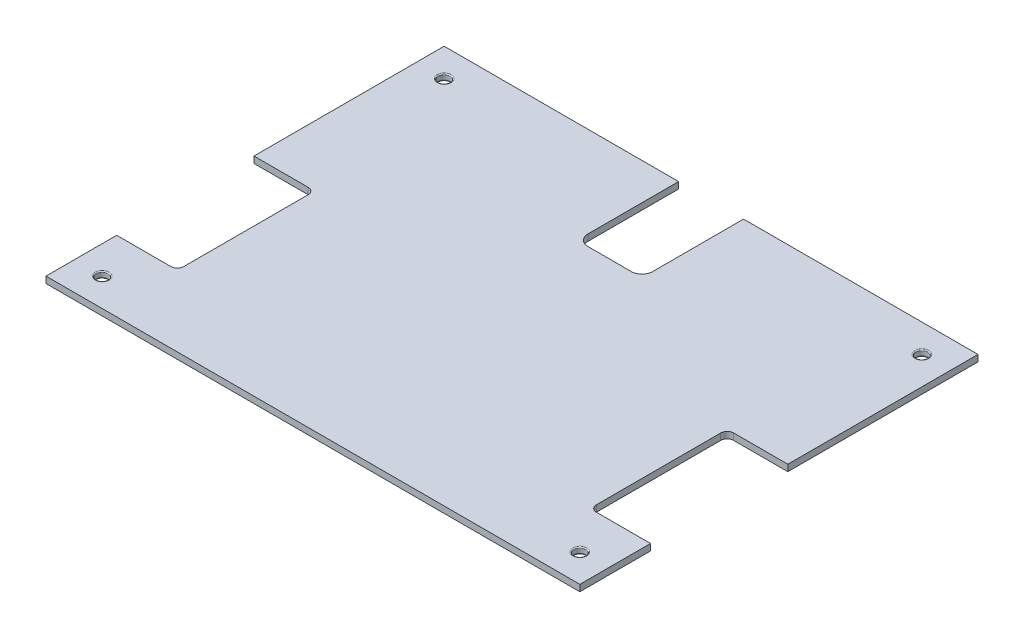
SolidWorks part; units mm, degrees
ref_plane "Front Plane" through (0, 0, 0) normal (0, 0, 1) x (1, 0, 0)
ref_plane "Top Plane" through (0, 0, 0) normal (0, 1, 0) x (1, 0, 0)
ref_plane "Right Plane" through (0, 0, 0) normal (1, 0, 0) x (0, 0, -1)
sketch "Sketch1" plane through (0, 0, 0) normal (0, 1, 0) x (1, 0, 0)
  line L1 (-123.65, -92.225) -> (123.65, -92.225)
  line L2 (-123.65, -92.225) -> (-123.65, 92.225)
  line L3 (-123.65, 92.225) -> (123.65, 92.225)
  line L4 (123.65, -92.225) -> (123.65, 92.225)
  line L5 (-123.65, -92.225) -> (123.65, 92.225) construction
  line L6 (-123.65, 92.225) -> (123.65, -92.225) construction
  point P0 (0, 0)
  dimension "D1" = 247.3
  dimension "D2" = 184.45
extrude "Boss-Extrude1" add sketch "Sketch1" along normal blind 3
sketch "Sketch4" [suppressed] plane through (0, 3, 0) normal (0, 1, 0) x (1, 0, 0)
  line L0 (0, 0) -> (0, -50000) construction
  line L5 (120.6, -102.1875) -> (100.6, -105.2375) construction
  line L15 (-123.65, -105.2375) -> (-120.6, -105.2375)
  line L16 (-123.65, -105.2375) -> (-123.65, -62.1875)
  line L21 (-123.65, -62.1875) -> (-120.6, -62.1875)
  line L23 (-120.6, -102.1875) -> (-120.6, -62.1875)
  line L24 (-123.65, -105.2375) -> (-120.6, -62.1875) construction
  line L25 (-123.65, -62.1875) -> (-120.6, -105.2375) construction
  line L34 (0, 0) -> (50000, 0) construction
  line L35 (-120.6, -105.2375) -> (-100.6, -105.2375)
  line L37 (-120.6, -102.1875) -> (-100.6, -102.1875)
  line L38 (-100.6, -105.2375) -> (-100.6, -102.1875)
  line L39 (-120.6, -105.2375) -> (-100.6, -102.1875) construction
  line L40 (-120.6, -102.1875) -> (-100.6, -105.2375) construction
  line L41 (120.6, -105.2375) -> (100.6, -102.1875) construction
  line L42 (123.65, -62.1875) -> (120.6, -105.2375) construction
  line L43 (123.65, -105.2375) -> (120.6, -62.1875) construction
  line L44 (100.6, -105.2375) -> (100.6, -102.1875)
  line L45 (120.6, -102.1875) -> (100.6, -102.1875)
  line L46 (120.6, -105.2375) -> (100.6, -105.2375)
  line L47 (120.6, -102.1875) -> (120.6, -62.1875)
  line L48 (123.65, -62.1875) -> (120.6, -62.1875)
  line L49 (123.65, -105.2375) -> (123.65, -62.1875)
  line L50 (123.65, -105.2375) -> (120.6, -105.2375)
  point P4 (-122.125, -83.7125)
  point P9 (-110.6, -103.7125)
  point P19 (110.6, -103.7125)
  point P20 (122.125, -83.7125)
  dimension "D1" = 43.05
  dimension "D2" = 3.05
  dimension "D3" = 3.05
  dimension "D4" = 23.05
extrude "Cut-Extrude2" [suppressed] cut sketch "Sketch4" against normal through all
sketch "Sketch2" plane through (0, 3, 0) normal (0, 1, 0) x (1, 0, 0)
  line L0 (0, 0) -> (50000, 0) construction
  line L1 (0, 0) -> (0, 50000) construction
  line L2 (-123.65, 92.225) -> (-123.65, -92.225) construction
  line L3 (123.65, 92.225) -> (-123.65, 92.225) construction
  circle A0 centre (-110.65, 79.225) radius 2.75
  circle A1 centre (110.65, 79.225) radius 2.75
  circle A2 centre (110.65, -79.225) radius 2.75
  circle A3 centre (-110.65, -79.225) radius 2.75
  dimension "D1" = 5.5
  dimension "D2" = 13
  dimension "D3" = 13
extrude "Cut-Extrude1" cut sketch "Sketch2" against normal through all
fillet "Fillet1" radius 0.5 8 edges at (-110.65, 3, -76.475) (-110.65, 0, -76.475) (110.65, 3, -81.975) (110.65, 0, -81.975) (110.65, 3, 81.975) (110.65, 0, 81.975) (-110.65, 3, 76.475) (-110.65, 0, 76.475)
sketch "Sketch5" plane through (0, 3, 0) normal (0, 1, 0) x (1, 0, 0)
  line L0 (123.65, 92.225) -> (-123.65, 92.225) construction
  line L1 (-15.05, 92.225) -> (15.05, 92.225)
  line L2 (-15.05, 92.225) -> (-15.05, 50.175)
  line L3 (-10.05, 45.175) -> (10.05, 45.175)
  line L4 (15.05, 92.225) -> (15.05, 50.175)
  line L5 (-15.05, 92.225) -> (15.05, 45.175) construction
  line L6 (-15.05, 45.175) -> (15.05, 92.225) construction
  arc A0 (-10.05, 45.175) -> (-15.05, 50.175) centre (-10.05, 50.175) cw
  arc A1 (15.05, 50.175) -> (10.05, 45.175) centre (10.05, 50.175) cw
  point P4 (0, 68.7)
  dimension "D3" = 5
  dimension "D4" = 5
  dimension "D1" = 30.1
  dimension "D2" = 47.05
extrude "Cut-Extrude3" cut sketch "Sketch5" against normal through all
sketch "Sketch6" plane through (0, 3, 0) normal (0, 1, 0) x (1, 0, 0)
  line L0 (-123.65, 92.225) -> (-123.65, -92.225) construction
  line L1 (-123.65, -59.475) -> (-98.57, -59.475)
  line L2 (-123.65, -59.475) -> (-123.65, 4.125)
  line L3 (-123.65, 4.125) -> (-98.57, 4.125)
  line L4 (-95.57, -56.475) -> (-95.57, 1.125)
  line L5 (-123.65, -92.225) -> (123.65, -92.225) construction
  line L6 (0, 0) -> (0, -50000) construction
  line L7 (95.57, -56.475) -> (95.57, 1.125)
  line L8 (123.65, 4.125) -> (98.57, 4.125)
  line L9 (123.65, -59.475) -> (123.65, 4.125)
  line L10 (123.65, -59.475) -> (98.57, -59.475)
  arc A0 (98.57, -59.475) -> (95.57, -56.475) centre (98.57, -56.475) cw
  arc A1 (95.57, 1.125) -> (98.57, 4.125) centre (98.57, 1.125) cw
  arc A2 (-98.57, -59.475) -> (-95.57, -56.475) centre (-98.57, -56.475) ccw
  arc A3 (-95.57, 1.125) -> (-98.57, 4.125) centre (-98.57, 1.125) ccw
  point P17 (95.57, -59.475)
  point P20 (95.57, 4.125)
  point P23 (-95.57, -59.475)
  point P26 (-95.57, 4.125)
  dimension "D4" = 3
  dimension "D1" = 32.75
  dimension "D2" = 63.6
  dimension "D3" = 28.08
extrude "Cut-Extrude4" cut sketch "Sketch6" against normal through all
sketch "Sketch7" [suppressed] plane through (0, 3, 0) normal (0, 1, 0) x (1, 0, 0)
  line L0 (-123.65, 15.0575) -> (-98.57, 15.0575)
  line L1 (-123.65, 15.0575) -> (-123.65, 78.6575)
  line L2 (-123.65, 78.6575) -> (-98.57, 78.6575)
  line L3 (-95.57, 18.0575) -> (-95.57, 75.6575)
  line L4 (123.65, 105.2375) -> (-123.65, 105.2375) construction
  line L5 (-123.65, 105.2375) -> (-123.65, -62.1875) construction
  line L6 (0, -1.65) -> (0, 1.65) construction
  line L7 (95.57, 18.0575) -> (95.57, 75.6575)
  line L8 (123.65, 78.6575) -> (98.57, 78.6575)
  line L9 (123.65, 15.0575) -> (123.65, 78.6575)
  line L10 (123.65, 15.0575) -> (98.57, 15.0575)
  arc A0 (98.57, 15.0575) -> (95.57, 18.0575) centre (98.57, 18.0575) cw
  arc A1 (95.57, 75.6575) -> (98.57, 78.6575) centre (98.57, 75.6575) cw
  arc A2 (-95.57, 18.0575) -> (-98.57, 15.0575) centre (-98.57, 18.0575) cw
  arc A3 (-95.57, 75.6575) -> (-98.57, 78.6575) centre (-98.57, 75.6575) ccw
  point P16 (95.57, 15.0575)
  point P19 (95.57, 78.6575)
  point P22 (-95.57, 15.0575)
  point P25 (-95.57, 78.6575)
  dimension "D4" = 3
  dimension "D1" = 63.6
  dimension "D2" = 28.08
  dimension "D3" = 26.58
extrude "Cut-Extrude5" [suppressed] cut sketch "Sketch7" against normal through all
sketch "Sketch8" [suppressed] plane through (0, 3, 0) normal (0, 1, 0) x (1, 0, 0)
  line L0 (-14.35, -33.2375) -> (-14.35, 49966.7625) construction
  line L1 (53.65, -55.2375) -> (-82.35, -55.2375) construction
  line L2 (53.65, -55.2375) -> (53.65, -11.2375) construction
  line L3 (53.65, -11.2375) -> (-82.35, -11.2375) construction
  line L4 (-82.35, -55.2375) -> (-82.35, -11.2375) construction
  line L5 (53.65, -55.2375) -> (-82.35, -11.2375) construction
  line L6 (53.65, -11.2375) -> (-82.35, -55.2375) construction
  line L7 (-14.35, -33.2375) -> (-50014.35, -33.2375) construction
  circle A0 centre (19.65, -55.2375) radius 1
  circle A1 centre (-14.35, -55.2375) radius 1
  circle A2 centre (-48.35, -55.2375) radius 1
  circle A3 centre (-48.35, -11.2375) radius 1
  circle A4 centre (-14.35, -11.2375) radius 1
  circle A5 centre (19.65, -11.2375) radius 1
  point P4 (-14.35, -33.2375)
  dimension "D1" = 2
  dimension "D3" = 34
extrude "Cut-Extrude6" [suppressed] cut sketch "Sketch8" against normal through all
fillet "Fillet2" [suppressed] radius 0.5
sketch "Sketch9" [suppressed] plane through (0, 3, 0) normal (0, 1, 0) x (1, 0, 0)
  circle A0 centre (-52.194, 74.8945) radius 1.35 construction
  circle A1 centre (5.806, 74.8945) radius 1.35 construction
  circle A2 centre (-74.85, 26.2625) radius 2.75 construction
  circle A3 centre (-52.194, 25.8945) radius 1.35 construction
  circle A4 centre (5.806, 25.8945) radius 1.35 construction
  circle A5 centre (40.15, 26.2625) radius 2.75 construction
  circle A6 centre (-52.194, 74.8945) radius 1.35
  circle A7 centre (5.806, 74.8945) radius 1.35
  circle A8 centre (-74.85, 26.2625) radius 2.75
  circle A9 centre (-52.194, 25.8945) radius 1.35
  circle A10 centre (5.806, 25.8945) radius 1.35
  circle A11 centre (40.15, 26.2625) radius 2.75
extrude "Cut-Extrude7" [suppressed] cut sketch "Sketch9" against normal through all
fillet "Fillet3" [suppressed] radius 0.5
sketch "Sketch10" [suppressed] plane through (0, 3, 0) normal (0, 1, 0) x (1, 0, 0)
  circle A0 centre (74.85, 69.2625) radius 2.75 construction
  circle A1 centre (-40.15, 69.2625) radius 2.75 construction
  circle A2 centre (74.85, 69.2625) radius 2.75
  circle A3 centre (-40.15, 69.2625) radius 2.75
extrude "Cut-Extrude8" [suppressed] cut sketch "Sketch10" against normal through all
fillet "Fillet4" [suppressed] radius 0.5
sketch "Sketch12" [suppressed] plane through (0, 3, 0) normal (0, 1, 0) x (1, 0, 0)
sketch "Sketch13" [suppressed] plane through (0, 3, 0) normal (0, 1, 0) x (1, 0, 0)
  line L0 (-100.6, -54.45) -> (100.6, -54.45) construction
  line L1 (-123.65, 54.45) -> (-123.65, -11.4) construction
  circle A0 centre (-83.65, -41.45) radius 2.75
  circle A2 centre (-33.65, -41.45) radius 2.75
  circle A3 centre (-33.65, 8.55) radius 2.75
  circle A4 centre (-83.65, 8.55) radius 2.75
  dimension "D1" = 5.5
  dimension "D2" = 13
  dimension "D3" = 40
  dimension "D4" = 2
  dimension "D5" = 2
extrude "Cut-Extrude9" [suppressed] cut sketch "Sketch13" against normal through all
fillet "Fillet5" [suppressed] radius 0.5
